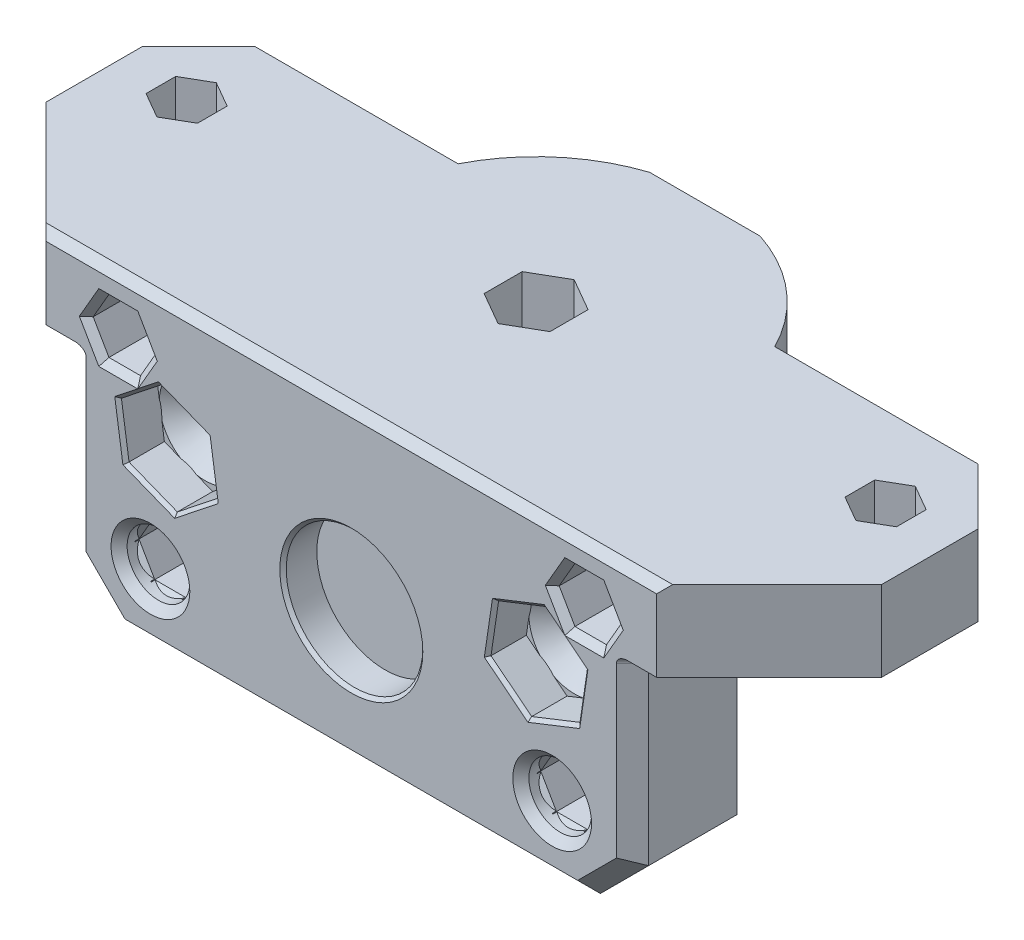
SolidWorks part; units mm, degrees
ref_plane "Front Plane" through (0, 0, 0) normal (0, 0, 1) x (1, 0, 0)
ref_plane "Top Plane" through (0, 0, 0) normal (0, 1, 0) x (1, 0, 0)
ref_plane "Right Plane" through (0, 0, 0) normal (1, 0, 0) x (0, 0, -1)
sketch "Sketch1" plane through (0, 0, 0) normal (0, 1, 0) x (1, 0, 0)
  circle A0 centre (0, 0) radius 8.05
  circle A1 centre (0, 0) radius 11.05
  dimension "D1" = 16.1
  dimension "D2" = 3
extrude "Boss-Extrude1" add sketch "Sketch1" along normal blind 5.5
sketch "Sketch2" plane through (0, 0, 0) normal (0, -1, 0) x (-1, 0, 0)
  circle A0 centre (0, 0) radius 6.05
  circle A1 centre (0, 0) radius 11.05
  dimension "D1" = 12.1
  dimension "D2" = 5
extrude "Boss-Extrude2" add sketch "Sketch2" along normal blind 5.9
sketch "Sketch3" plane through (0, -5.9, 0) normal (0, -1, 0) x (-1, 0, 0)
  circle A0 centre (0, 0) radius 8.05
  circle A1 centre (0, 0) radius 11.05
  dimension "D1" = 16.1
  dimension "D2" = 3
extrude "Boss-Extrude3" add sketch "Sketch3" along normal blind 3
sketch "Sketch5" plane through (0, 5.5, 0) normal (0, 1, 0) x (1, 0, 0)
  line L0 (9.8541, 5) -> (27, 5)
  line L1 (-27, -5) -> (-9.8541, -5)
  line L2 (-27, -5) -> (-27, 5)
  line L3 (-27, 5) -> (-9.8541, 5)
  line L4 (27, -5) -> (27, 5)
  line L5 (9.8541, -5) -> (27, -5)
  line L7 (0, 2.3671) -> (-2.05, 1.1836)
  line L8 (-2.05, 1.1836) -> (-2.05, -1.1836)
  line L9 (-2.05, -1.1836) -> (0, -2.3671)
  line L10 (0, -2.3671) -> (2.05, -1.1836)
  line L11 (2.05, -1.1836) -> (2.05, 1.1836)
  line L12 (2.05, 1.1836) -> (0, 2.3671)
  line L13 (-21.75, 1.8475) -> (-23.35, 0.9238)
  line L14 (-23.35, 0.9238) -> (-23.35, -0.9238)
  line L15 (-23.35, -0.9238) -> (-21.75, -1.8475)
  line L16 (-21.75, -1.8475) -> (-20.15, -0.9238)
  line L17 (-20.15, -0.9238) -> (-20.15, 0.9238)
  line L18 (-20.15, 0.9238) -> (-21.75, 1.8475)
  line L19 (21.75, 1.8475) -> (20.15, 0.9238)
  line L20 (20.15, 0.9238) -> (20.15, -0.9238)
  line L21 (20.15, -0.9238) -> (21.75, -1.8475)
  line L22 (21.75, -1.8475) -> (23.35, -0.9238)
  line L23 (23.35, -0.9238) -> (23.35, 0.9238)
  line L24 (23.35, 0.9238) -> (21.75, 1.8475)
  circle A0 centre (0, 0) radius 11.05 construction
  circle A1 centre (-21.75, 0) radius 1.5
  circle A2 centre (21.75, 0) radius 1.5
  circle A3 centre (0, 0) radius 2.05
  circle A4 centre (0, 0) radius 11.05
  circle A5 centre (0, 0) radius 2.05 construction
  circle A6 centre (-21.75, 0) radius 1.6 construction
  circle A7 centre (21.75, 0) radius 1.6 construction
  circle M6 centre (0, 0) radius 11.05
  circle M7 centre (0, 0) radius 8.05
  dimension "D5" = 3
  dimension "D8" = 4.1
  dimension "D11" = 22.1
  dimension "D12" = 4.1
  dimension "D13" = 3.2
  dimension "D14" = 3.2
  dimension "D1" = 10
  dimension "D2" = 54
  dimension "D3" = 27
  dimension "D4" = 5
  dimension "D6" = 5.25
  dimension "D9" = 5
  dimension "D10" = 27
  dimension "D7" = 2
extrude "Boss-Extrude5" add sketch "Sketch5" along normal blind 5 contours L3 L2 L1 A1 M6 | M6 M7 | L5 L4 L0 A2 M6 | A3 M7 region at (18.6586, 5.5, 0) region at (10.4429, 5.5, -2.4978) region at (-18.6586, 5.5, 0) region at (-7.8223, 5.5, 0)
sketch "Sketch6" plane through (0, 10.5, 0) normal (0, 1, 0) x (1, 0, 0)
  line L0 (-27, -5) -> (-9.8541, -5) construction
  line L1 (-15.5, -5) -> (-9.8541, -5)
  line L2 (-15.5, -5) -> (-15.5, -15)
  line L3 (-15.5, -15) -> (15.5, -15)
  line L4 (15.5, -5) -> (15.5, -15)
  line L5 (9.8541, -5) -> (15.5, -5)
  arc A1 (-9.8541, -5) -> (9.8541, -5) centre (0, 0) ccw
  dimension "D4" = 11.05
  dimension "D1" = 31
  dimension "D3" = 10
extrude "Boss-Extrude6" add sketch "Sketch6" against normal blind 28
sketch "Sketch7" plane through (0, 0, 15) normal (0, 0, 1) x (1, 0, 0)
  line L0 (-15.5, -17.5) -> (15.5, -17.5) construction
  line L1 (-15.5, -17.5) -> (-15.5, 10.5) construction
  circle A0 centre (-12, -14) radius 1.6
  circle A1 centre (12, -14) radius 1.6
  dimension "D4" = 3.2
  dimension "D1" = 3.5
  dimension "D2" = 3.5
  dimension "D3" = 2
extrude "Cut-Extrude1" cut sketch "Sketch7" against normal blind 10
sketch "Sketch19" plane through (0, 0, 15) normal (0, 0, 1) x (1, 0, 0)
  circle A0 centre (-12, -14) radius 2.25
  circle A1 centre (12, -14) radius 2.25
  dimension "D1" = 4.5
  dimension "D2" = 4.5
extrude "Cut-Extrude12" cut sketch "Sketch19" against normal blind 7.2
sketch "Sketch8" plane through (0, -17.5, 0) normal (0, -1, 0) x (-1, 0, 0)
  line L0 (15.5, -15) -> (-15.5, -15) construction
  line L1 (-8, -15) -> (8, -15)
  line L2 (-8, -15) -> (-8, -5)
  line L3 (-8, -5) -> (8, -5)
  line L4 (8, -15) -> (8, -5)
  circle A0 centre (0, 0) radius 12
  point P6 (0, -15)
  line M6 (15.5, -5) -> (9.8541, -5)
  arc M7 (9.8541, -5) -> (-9.8541, -5) centre (0, 0) cw
  line M8 (-9.8541, -5) -> (-15.5, -5)
  line M10 (-15.5, -15) -> (15.5, -15)
  dimension "D4" = 24
  dimension "D1" = 10
  dimension "D2" = 16
  dimension "D3" = 0
extrude "Cut-Extrude2" cut sketch "Sketch8" against normal blind 7 contours A0 L2 L4 M10 | L2 A0 L4 M7 | L4 L3 L2 M7 | A0 L2 M8 M7 | L4 A0 M6 M7 region at (0, -17.5, 12.9198) region at (9.3108, -17.5, 6.7422) region at (7.8341, -17.5, 8.2834) region at (-9.3108, -17.5, 6.7422) region at (0, -17.5, 7.5931)
ref_plane "Plane1" through (0, 0, 0.1) normal (0, 0, 1) x (1, 0, 0)
sketch "Sketch11" plane through (0, 0, 0.1) normal (0, 0, 1) x (1, 0, 0)
  line L0 (9.8541, 5.5) -> (27, 5.5) construction
  line L1 (33.7519, -27.3661) -> (-35.342, -27.3661)
  line L2 (33.7519, -27.3661) -> (33.7519, 5.5)
  line L3 (33.7519, 5.5) -> (-35.342, 5.5)
  line L4 (-35.342, -27.3661) -> (-35.342, 5.5)
  dimension "D1" = 0
extrude "Cut-Extrude4" cut sketch "Sketch11" against normal through all
sketch "Sketch12" plane through (0, 0, 15) normal (0, 0, 1) x (1, 0, 0)
  line L0 (-15.5, -17.5) -> (-15.5, 10.5) construction
  line L1 (15.5, -17.5) -> (15.5, 10.5) construction
  line L2 (-15.5, 10.5) -> (15.5, 10.5) construction
  circle A0 centre (-11.5, 2.5) radius 1.65
  circle A1 centre (11.5, 2.5) radius 1.65
  dimension "D1" = 3.3
  dimension "D2" = 3.3
  dimension "D3" = 4
  dimension "D4" = 4
  dimension "D5" = 8
  dimension "D6" = 8
extrude "Cut-Extrude5" cut sketch "Sketch12" against normal through all
sketch "Sketch13" plane through (0, 0, 15) normal (0, 0, 1) x (1, 0, 0)
  circle A0 centre (-11.5, 2.5) radius 2.25
  circle A1 centre (11.5, 2.5) radius 2.25
  dimension "D1" = 4.5
  dimension "D2" = 4.5
extrude "Cut-Extrude6" cut sketch "Sketch13" against normal blind 4.2
sketch "Sketch18" plane through (0, 5.5, 0) normal (0, -1, 0) x (-1, 0, 0)
  line L1 (-21.75, 3.2332) -> (-24.55, 1.6166)
  line L2 (-24.55, 1.6166) -> (-24.55, -1.6166)
  line L3 (-24.55, -1.6166) -> (-21.75, -3.2332)
  line L4 (-21.75, -3.2332) -> (-18.95, -1.6166)
  line L5 (-18.95, -1.6166) -> (-18.95, 1.6166)
  line L6 (-18.95, 1.6166) -> (-21.75, 3.2332)
  line L7 (21.811, 3.1274) -> (19.011, 1.5108)
  line L8 (19.011, 1.5108) -> (19.011, -1.7223)
  line L9 (19.011, -1.7223) -> (21.811, -3.3389)
  line L10 (21.811, -3.3389) -> (24.611, -1.7223)
  line L11 (24.611, -1.7223) -> (24.611, 1.5108)
  line L12 (24.611, 1.5108) -> (21.811, 3.1274)
  circle A0 centre (-21.75, 0) radius 2.8 construction
  circle A1 centre (21.811, -0.1057) radius 2.8 construction
  dimension "D1" = 5.6
  dimension "D2" = 5.6
extrude "Cut-Extrude11" cut sketch "Sketch18" against normal blind 2
sketch "Sketch20" plane through (0, 0, 15) normal (0, 0, 1) x (1, 0, 0)
  line L0 (-15.5, -17.5) -> (-15.5, 10.5) construction
  line L1 (15.5, -17.5) -> (-15.5, -17.5)
  line L2 (15.5, -17.5) -> (15.5, -8.9)
  line L3 (15.5, -8.9) -> (-15.5, -8.9)
  line L4 (-15.5, -17.5) -> (-15.5, -8.9)
  line L5 (8, -8.9) -> (-8, -8.9) construction
  dimension "D1" = 0
extrude "Cut-Extrude13" cut sketch "Sketch20" against normal blind 3
sketch "Sketch25" plane through (0, 0, 5) normal (0, 0, 1) x (1, 0, 0)
  line L1 (15.5, 10.5) -> (27, 10.5)
  line L2 (15.5, 10.5) -> (15.5, 5.5)
  line L3 (15.5, 5.5) -> (27, 5.5)
  line L4 (27, 10.5) -> (27, 5.5)
  line L5 (-15.5, 5.5) -> (-27, 5.5)
  line L6 (-15.5, 5.5) -> (-15.5, 10.5)
  line L7 (-15.5, 10.5) -> (-27, 10.5)
  line L8 (-27, 5.5) -> (-27, 10.5)
extrude "Boss-Extrude7" add sketch "Sketch25" along normal blind 3.3
sketch "草图1" plane through (0, 0, 15) normal (0, 0, 1) x (1, 0, 0)
  line L1 (-15.5, 10.5) -> (15.5, 10.5)
  line L2 (-15.5, 10.5) -> (-15.5, -17.5)
  line L3 (-15.5, -17.5) -> (15.5, -17.5)
  line L4 (15.5, 10.5) -> (15.5, -17.5)
extrude "切除-拉伸1" cut sketch "草图1" against normal blind 3.5
sketch "草图2" plane through (0, -17.5, 0) normal (0, -1, 0) x (-1, 0, 0)
  line L1 (15.5, -11.5) -> (-15.5, -11.5)
  line L2 (15.5, -11.5) -> (15.5, -5)
  line L3 (15.5, -5) -> (-15.5, -5)
  line L4 (-15.5, -11.5) -> (-15.5, -5)
extrude "切除-拉伸2" cut sketch "草图2" against normal up to surface (8.6 mm away) up to face at (0, -8.9, 4.0897)
sketch "草图3" plane through (0, 0, 11.5) normal (0, 0, 1) x (1, 0, 0)
  line L1 (-8.4932, 1.3116) -> (-8.9674, 4.5098)
  line L2 (-8.9674, 4.5098) -> (-11.9742, 5.6982)
  line L3 (-11.9742, 5.6982) -> (-14.5068, 3.6884)
  line L4 (-14.5068, 3.6884) -> (-14.0326, 0.4902)
  line L5 (-14.0326, 0.4902) -> (-11.0258, -0.6982)
  line L6 (-11.0258, -0.6982) -> (-8.4932, 1.3116)
  line L7 (8.4932, 1.3116) -> (11.0258, -0.6982)
  line L8 (11.0258, -0.6982) -> (14.0326, 0.4902)
  line L9 (14.0326, 0.4902) -> (14.5068, 3.6884)
  line L10 (14.5068, 3.6884) -> (11.9742, 5.6982)
  line L11 (11.9742, 5.6982) -> (8.9674, 4.5098)
  line L12 (8.9674, 4.5098) -> (8.4932, 1.3116)
  circle A2 centre (-11.5, 2.5) radius 2.8 construction
  circle A3 centre (11.5, 2.5) radius 2.8 construction
  dimension "D1" = 5.6
  dimension "D2" = 5.6
extrude "切除-拉伸3" cut sketch "草图3" against normal blind 2.4
chamfer "倒角1" distance 1.2 angle 45 2 edges at (13.15, 2.5, 9.1) (-9.85, 2.5, 9.1)
sketch "草图4" plane through (0, 0, 11.5) normal (0, 0, 1) x (1, 0, 0)
  line L0 (-15.5, 10.5) -> (-15.5, -8.9) construction
  line L1 (-15.5, -8.9) -> (15.5, -8.9) construction
  line L2 (15.5, -8.9) -> (15.5, 10.5) construction
  circle A0 centre (-12.5, -4.4) radius 1.95
  circle A1 centre (12.5, -4.4) radius 1.95
  dimension "D1" = 3.9
  dimension "D3" = 4.5
  dimension "D4" = 3.9
  dimension "D5" = 4.5
  dimension "D6" = 3
  dimension "D2" = 3
extrude "切除-拉伸4" cut sketch "草图4" against normal blind 1
sketch "草图10" plane through (0, 0, 10.5) normal (0, 0, 1) x (1, 0, 0)
  line L1 (-10.537, -4.4) -> (-11.5185, -2.7)
  line L2 (-11.5185, -2.7) -> (-13.4815, -2.7)
  line L3 (-13.4815, -2.7) -> (-14.463, -4.4)
  line L4 (-14.463, -4.4) -> (-13.4815, -6.1)
  line L5 (-13.4815, -6.1) -> (-11.5185, -6.1)
  line L6 (-11.5185, -6.1) -> (-10.537, -4.4)
  line L7 (14.463, -4.4) -> (13.4815, -2.7)
  line L8 (13.4815, -2.7) -> (11.5185, -2.7)
  line L9 (11.5185, -2.7) -> (10.537, -4.4)
  line L10 (10.537, -4.4) -> (11.5185, -6.1)
  line L11 (11.5185, -6.1) -> (13.4815, -6.1)
  line L12 (13.4815, -6.1) -> (14.463, -4.4)
  circle A0 centre (-12.5, -4.4) radius 1.7 construction
  circle A1 centre (12.5, -4.4) radius 1.7 construction
  dimension "D1" = 3.4
  dimension "D2" = 3.4
extrude "切除-拉伸7" cut sketch "草图10" against normal through all
sketch "草图12" plane through (0, 0, 11.5) normal (0, 0, 1) x (1, 0, 0)
  circle A0 centre (0, -0.4) radius 4.25
  circle A2 centre (-12.5, -4.4) radius 1.95 construction
  circle A3 centre (-12.5, -4.4) radius 1.95 construction
  dimension "D1" = 8.5
  dimension "D2" = 12.5
  dimension "D3" = 4
extrude "切除-拉伸12" cut sketch "草图12" against normal blind 2.1
chamfer "倒角7" distance 0.25 angle 45 6 edges at (-12.5, -6.1, 10.5) (-13.9722, -5.25, 10.5) (-11.0278, -5.25, 10.5) (-11.0278, -3.55, 10.5) (-13.9722, -3.55, 10.5) (-12.5, -2.7, 10.5)
chamfer "倒角8" distance 0.25 angle 45 6 edges at (13.9722, -5.25, 10.5) (12.5, -6.1, 10.5) (11.0278, -5.25, 10.5) (13.9722, -3.55, 10.5) (11.0278, -3.55, 10.5) (12.5, -2.7, 10.5)
ref_axis "基准轴1" through (9.8541, 10.5, -5) along (1, 0, 0)
ref_plane "基准面1" through (0, 7.75, -7.75) normal (0, 0.7071, -0.7071) x (1, 0, 0)
ref_plane "基准面2" through (0, 10.5006, -10.5006) normal (0, 0.7071, -0.7071) x (1, 0, 0)
sketch "草图11" plane through (0, 10.5006, -10.5006) normal (0, 0.7071, -0.7071) x (1, 0, 0)
  line L1 (-14.5081, 8.4609) -> (16.7, 8.4609)
  line L2 (-14.5081, 8.4609) -> (-14.5081, -7.7078)
  line L3 (-14.5081, -7.7078) -> (16.7, -7.7078)
  line L4 (16.7, 8.4609) -> (16.7, -7.7078)
extrude "切除-拉伸9" cut sketch "草图11" along normal through all
sketch "草图5" plane through (-15.5, 0, 0) normal (-1, 0, 0) x (0, 0, 1)
  line L1 (5, 5.5) -> (11.5, 5.5)
  line L2 (5, 5.5) -> (5, -8.9)
  line L3 (5, -8.9) -> (11.5, -8.9)
  line L4 (11.5, 5.5) -> (11.5, -8.9)
  line L5 (8.3, 10.5) -> (11.5, 10.5)
  line L6 (8.3, 10.5) -> (8.3, 5.5)
  line L7 (8.3, 5.5) -> (11.5, 5.5)
  line L8 (11.5, 10.5) -> (11.5, 5.5)
  line M1 (5, 5.5) -> (5, -8.9)
  line M2 (5, -8.9) -> (11.5, -8.9)
  line M3 (11.5, -8.9) -> (11.5, 10.5)
  line M4 (11.5, 10.5) -> (8.3, 10.5)
  line M5 (8.3, 10.5) -> (8.3, 5.5)
  line M6 (8.3, 5.5) -> (5, 5.5)
extrude "凸台-拉伸1" add sketch "草图5" along normal blind 2 contours L1 M6 M1 M2 M3 | L1 M5 M3 M4 region at (-15.5, -1.7, 8.25) region at (-15.5, 8, 9.9)
sketch "草图6" plane through (15.5, 0, 0) normal (1, 0, 0) x (0, 0, -1)
  line L9 (-5, 5.5) -> (-11.5, 5.5)
  line L10 (-5, 5.5) -> (-5, -8.9)
  line L11 (-5, -8.9) -> (-11.5, -8.9)
  line L12 (-11.5, 5.5) -> (-11.5, -8.9)
  line L13 (-11.5, 10.5) -> (-8.3, 10.5)
  line L14 (-11.5, 10.5) -> (-11.5, 5.5)
  line L15 (-11.5, 5.5) -> (-8.3, 5.5)
  line L16 (-8.3, 10.5) -> (-8.3, 5.5)
  line M1 (-11.5, 10.5) -> (-11.5, -8.9)
  line M2 (-11.5, -8.9) -> (-5, -8.9)
  line M3 (-5, -8.9) -> (-5, 5.5)
  line M4 (-5, 5.5) -> (-8.3, 5.5)
  line M5 (-8.3, 5.5) -> (-8.3, 10.5)
  line M6 (-8.3, 10.5) -> (-11.5, 10.5)
extrude "凸台-拉伸2" add sketch "草图6" along normal blind 2 contours L9 M5 M6 M1 | L9 M4 M1 M2 M3 region at (15.5, -1.7, 8.25) region at (15.5, 8, 9.9)
chamfer "倒角3" distance 4.5 angle 45 2 edges at (27, 8, -5) (-27, 8, -5)
sketch "草图8" plane through (0, 0, 8.3) normal (0, 0, 1) x (1, 0, 0)
  line L1 (-27, 10.5) -> (-17.5, 10.5)
  line L2 (-27, 10.5) -> (-27, 5.5)
  line L3 (-27, 5.5) -> (-17.5, 5.5)
  line L4 (-17.5, 10.5) -> (-17.5, 5.5)
  line L5 (27, 10.5) -> (17.5, 10.5)
  line L6 (27, 10.5) -> (27, 5.5)
  line L7 (27, 5.5) -> (17.5, 5.5)
  line L8 (17.5, 10.5) -> (17.5, 5.5)
extrude "凸台-拉伸3" add sketch "草图8" along normal up to surface (3.2 mm away) up to face at (4.25, -0.4, 11.5)
chamfer "倒角4" distance 8 angle 45 2 edges at (27, 8, 11.5) (-27, 8, 11.5)
sketch "草图9" plane through (0, 10.5, 0) normal (0, 1, 0) x (1, 0, 0)
  line L0 (-27, -3.5) -> (-27, 0.5) construction
  line L1 (-32.8717, 7.8341) -> (-26, 7.8341)
  line L2 (-32.8717, 7.8341) -> (-32.8717, -8.0819)
  line L3 (-32.8717, -8.0819) -> (-26, -8.0819)
  line L4 (-26, 7.8341) -> (-26, -8.0819)
  line L5 (30.9516, 7.0761) -> (26, 7.0761)
  line L6 (30.9516, 7.0761) -> (30.9516, -6.5661)
  line L7 (30.9516, -6.5661) -> (26, -6.5661)
  line L8 (26, 7.0761) -> (26, -6.5661)
  line L9 (27, -3.5) -> (27, 0.5) construction
  point P12 (27, -1.5)
  dimension "D1" = 1
  dimension "D2" = 1
extrude "切除-拉伸6" cut sketch "草图9" against normal through all
chamfer "倒角5" distance 3 angle 45 2 edges at (17.5, -8.9, 8.25) (-17.5, -8.9, 8.25)
chamfer "倒角6" distance 1 angle 45 5 edges at (17.5, -0.2, 11.5) (16, -7.4, 11.5) (-16, -7.4, 11.5) (-17.5, -0.2, 11.5) (0, -8.9, 11.5)
fillet "圆角2" radius 0.5 2 edges at (-17, 5.5, 11) (17, 5.5, 11)
chamfer "倒角9" distance 0.5 angle 45 2 edges at (-10.55, -4.4, 11.5) (14.45, -4.4, 11.5)
chamfer "倒角10" distance 0.5 angle 45 1 edges at (0, 10.5, 11.5)
chamfer "倒角11" distance 0.2 angle 45 25 edges at (9.7595, 0.3067, 11.5) (12.5292, -0.104, 11.5) (14.2697, 2.0893, 11.5) (13.2405, 4.6933, 11.5) (10.4708, 5.104, 11.5) (8.7303, 2.9107, 11.5) (-8.7303, 2.9107, 11.5) (-9.7595, 0.3067, 11.5) (-12.5292, -0.104, 11.5) (-14.2697, 2.0893, 11.5) (-13.2405, 4.6933, 11.5) (-10.4708, 5.104, 11.5) (20.35, 5.5, -2.4249) (23.15, 5.5, -2.4249) (24.55, 5.5, 0) (23.15, 5.5, 2.4249) (20.35, 5.5, 2.4249) (18.95, 5.5, 0) (-20.411, 5.5, 2.5306) (-19.011, 5.5, 0.1057) (-20.411, 5.5, -2.3191) (-23.211, 5.5, -2.3191) (-24.611, 5.5, 0.1057) (-23.211, 5.5, 2.5306) (4.25, -0.4, 11.5)
sketch "草图14" plane through (0, 0, 5) normal (0, 0, -1) x (-1, 0, 0)
  line L1 (-17.5, 5.5) -> (-11.05, 5.5)
  line L2 (-17.5, 5.5) -> (-17.5, 3)
  line L3 (-17.5, 3) -> (-11.05, 3)
  line L4 (-11.05, 5.5) -> (-11.05, 3)
  line L5 (17.5, 5.5) -> (11.05, 5.5)
  line L6 (17.5, 5.5) -> (17.5, 3)
  line L7 (17.5, 3) -> (11.05, 3)
  line L8 (11.05, 5.5) -> (11.05, 3)
  circle A0 centre (-11.5, 2.5) radius 1.65
  circle A1 centre (11.5, 2.5) radius 1.65
  line M9 (-17.5, 5.5) -> (-17.5, -5.9)
  arc M13 (-9.8541, 2.3843) -> (-9.8541, 2.6157) centre (-11.5, 2.5) cw
  line M14 (-9.8541, 2.6157) -> (-9.8541, 5.5)
  line M15 (-9.8541, 5.5) -> (-17.5, 5.5)
  dimension "D1" = 2.5
  dimension "D2" = 2.5
  dimension "D3" = 6.45
  dimension "D4" = 6.45
extrude "凸台-拉伸5" add sketch "草图14" along normal up to surface (10 mm away) contours L3 M9 M13 M14 M15 | A1 L7 L6 L5 L8 region at (14.5805, 4.3461, 5) region at (-14.5805, 4.3461, 5) up to face at (16.177, 8, -5)
sketch "草图13" plane through (0, 0, 11.5) normal (0, 0, 1) x (1, 0, 0)
  line L0 (-19.5, 10.5) -> (19.5, 10.5) construction
  line L1 (12.537, 7) -> (13.5185, 5.3)
  line L2 (13.5185, 5.3) -> (15.4815, 5.3)
  line L3 (15.4815, 5.3) -> (16.463, 7)
  line L4 (16.463, 7) -> (15.4815, 8.7)
  line L5 (15.4815, 8.7) -> (13.5185, 8.7)
  line L6 (13.5185, 8.7) -> (12.537, 7)
  line L7 (19, 5.5) -> (19, 10) construction
  line L8 (0, 10) -> (0, 4.9865) construction
  line L9 (19, 10) -> (-19, 10) construction
  line L10 (-13.5185, 8.7) -> (-12.537, 7)
  line L11 (-15.4815, 8.7) -> (-13.5185, 8.7)
  line L12 (-16.463, 7) -> (-15.4815, 8.7)
  line L13 (-15.4815, 5.3) -> (-16.463, 7)
  line L14 (-13.5185, 5.3) -> (-15.4815, 5.3)
  line L15 (-12.537, 7) -> (-13.5185, 5.3)
  circle A0 centre (14.5, 7) radius 1.7 construction
  dimension "D1" = 3.5
  dimension "D3" = 3.4
  dimension "D2" = 4.5
extrude "切除-拉伸13" cut sketch "草图13" against normal through all
chamfer "倒角12" distance 1 angle 45 2 edges at (-17.5, 5.5, 3.1036) (17.5, 5.5, 3.1036)
chamfer "倒角13" distance 0.4 angle 45 12 edges at (13.0278, 6.15, 11.5) (14.5, 5.3, 11.5) (15.9722, 6.15, 11.5) (15.9722, 7.85, 11.5) (14.5, 8.7, 11.5) (13.0278, 7.85, 11.5) (-13.0278, 6.15, 11.5) (-14.5, 5.3, 11.5) (-15.9722, 6.15, 11.5) (-15.9722, 7.85, 11.5) (-14.5, 8.7, 11.5) (-13.0278, 7.85, 11.5)
equation "\"D3@Sketch5\"=\"D2@Sketch5\"/2"
equation "\"D4@Sketch5\"=\"D1@Sketch5\"/2"
equation "\"D6@Sketch5\"=\"D2@Sketch5\"/2-43.5/2"
equation "\"D9@Sketch5\"=\"D4@Sketch5\""
equation "\"D10@Sketch5\"=\"D3@Sketch5\""
equation "\"D1@Sketch6\"=30+1"
equation "\"`1\"=2"
